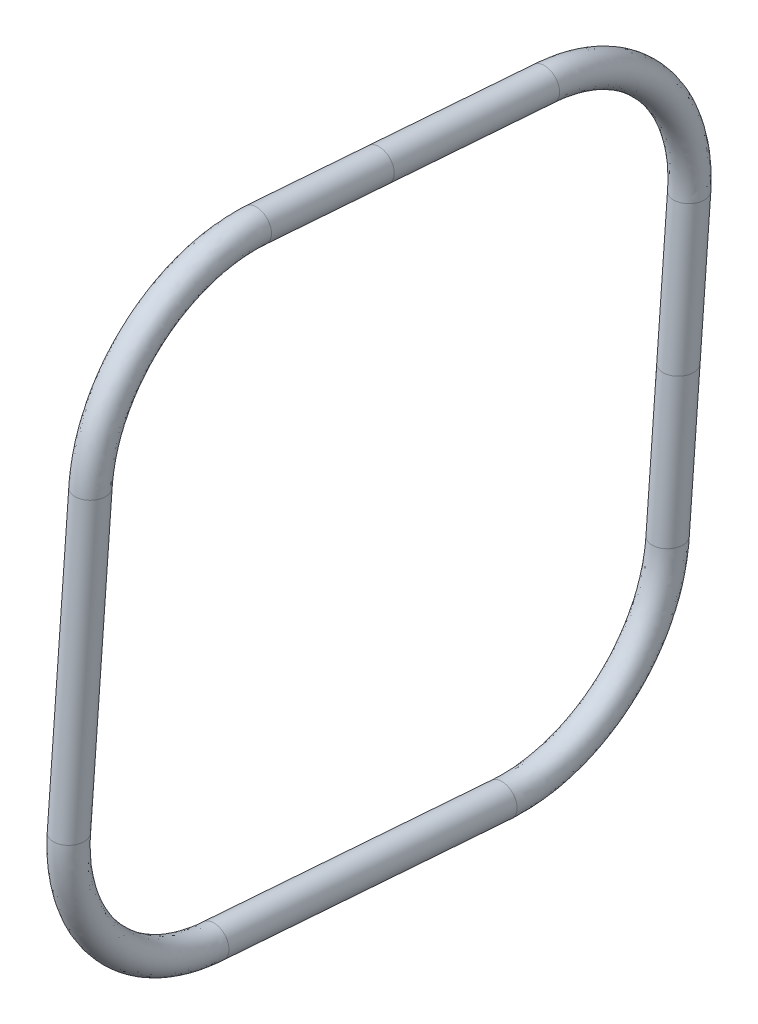
SolidWorks part; units mm, degrees
material "Rubber"
ref_plane "Front Plane" through (0, 0, 0) normal (0, 0, 1) x (1, 0, 0)
ref_plane "Top Plane" through (0, 0, 0) normal (0, 1, 0) x (1, 0, 0)
ref_plane "Right Plane" through (0, 0, 0) normal (1, 0, 0) x (0, 0, -1)
sketch "Sketch4" plane through (0, 0, 0) normal (1, 0, 0) x (0, 0, -1)
  line L0 (-33.6475, -14.0193) -> (-31.1849, 18.8731) construction
  line L1 (14.0193, -33.6475) -> (-18.8731, -31.1849) construction
  line L2 (-31.1849, 18.8731) -> (-31.0583, 18.8636)
  line L3 (-14.0288, 33.5208) -> (-14.0193, 33.6475)
  line L6 (32.4162, -2.4269) -> (31.1849, -18.8731) construction
  line L7 (33.6475, 14.0193) -> (32.4162, -2.4269) construction
  line L8 (-14.0193, 33.6475) -> (18.8731, 31.1849) construction
  line L9 (-33.6475, -14.0193) -> (-31.1849, 18.8731)
  line L10 (14.0193, -33.6475) -> (-18.8731, -31.1849)
  line L11 (32.4162, -2.4269) -> (31.1849, -18.8731)
  line L12 (33.6475, 14.0193) -> (32.4162, -2.4269)
  line L13 (-14.0193, 33.6475) -> (18.8731, 31.1849)
  arc A0 (-33.6475, -14.0193) -> (-18.8731, -31.1849) centre (-17.6775, -15.2149) ccw construction
  arc A1 (14.0193, -33.6475) -> (31.1849, -18.8731) centre (15.2149, -17.6775) ccw construction
  arc A2 (-14.0193, 33.6475) -> (-31.1849, 18.8731) centre (-15.2149, 17.6775) ccw
  arc A3 (-14.0288, 33.5208) -> (-31.0583, 18.8636) centre (-15.2149, 17.6775) ccw
  arc A4 (-14.0193, 33.6475) -> (-31.1849, 18.8731) centre (-15.2149, 17.6775) ccw
  arc A6 (33.6475, 14.0193) -> (18.8731, 31.1849) centre (17.6775, 15.2149) ccw construction
  arc A7 (-33.6475, -14.0193) -> (-18.8731, -31.1849) centre (-17.6775, -15.2149) ccw
  arc A8 (14.0193, -33.6475) -> (31.1849, -18.8731) centre (15.2149, -17.6775) ccw
  arc A9 (33.6475, 14.0193) -> (18.8731, 31.1849) centre (17.6775, 15.2149) ccw
  dimension "D1" = 0
sketch "Sketch3" plane through (0, 0, 0) normal (0, 0, 1) x (1, 0, 0)
  line L0 (0, 0) -> (-7.1671, 0) construction
  line L3 (-1.7399, 34.1034) -> (-1.7399, 31.6409) construction
  line L4 (-1.7399, 37.2442) -> (-1.7399, 34.7817) construction
  line L5 (-1.7399, 34.1034) -> (-1.7399, 31.6409)
  line L6 (0, 34.3632) -> (0, 0)
  line L7 (-1.7399, 37.2442) -> (-1.7399, 34.7817)
  line L8 (-1.7399, 34.1034) -> (-1.7399, 34.7817)
  ellipse E0 centre (0, 34.3632) end of major axis (0, 32.5979) minor radius 1.7399
  point P13 (0, 0)
  point P14 (0, 35.3287)
  point P15 (1.7653, 33.9788)
  point P16 (0, 35.3948)
  point P17 (0, 35.3778)
  point P19 (0, 36.353)
  point P20 (0, 0)
  point P21 (0, 35.9469)
  point P22 (0, 36.2818)
  point P23 (0, 36.0835)
  dimension "D1" = 3.5306
  dimension "D2" = 3.4798
ref_axis "Axis1" through (0, 0, 0) along (-1, 0, 0)
sweep "Sweep3" add profiles "Sketch3" path "Sketch4"
